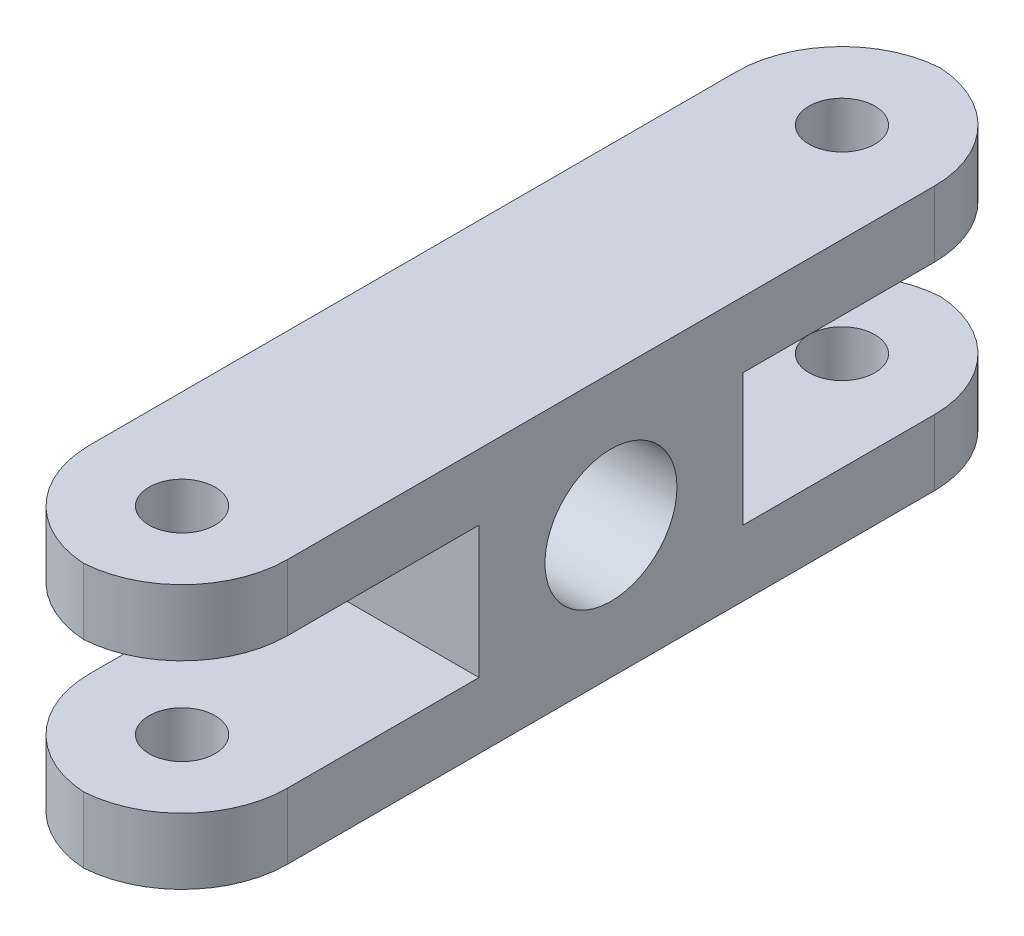
SolidWorks part; units mm, degrees
ref_plane "Front Plane" through (0, 0, 0) normal (0, 0, 1) x (1, 0, 0)
ref_plane "Top Plane" through (0, 0, 0) normal (0, 1, 0) x (1, 0, 0)
ref_plane "Right Plane" through (0, 0, 0) normal (1, 0, 0) x (0, 0, -1)
sketch "Sketch1" plane through (0, 0, 0) normal (0, 1, 0) x (1, 0, 0)
  line L1 (-7.5, -32.5) -> (7.5, -32.5)
  line L2 (-7.5, -32.5) -> (-7.5, 32.5)
  line L3 (-7.5, 32.5) -> (7.5, 32.5)
  line L4 (7.5, -32.5) -> (7.5, 32.5)
  line L5 (-7.5, -32.5) -> (7.5, 32.5) construction
  line L6 (-7.5, 32.5) -> (7.5, -32.5) construction
  point P0 (0, 0)
  dimension "D1" = 15
  dimension "D2" = 65
extrude "Boss-Extrude1" add sketch "Sketch1" along normal blind 20
sketch "Sketch2" plane through (0, 20, 0) normal (0, 1, 0) x (1, 0, 0)
  line L0 (-7.5, 0) -> (7.5, 0)
  line L1 (-7.5, 32.5) -> (-7.5, -32.5) construction
  line L2 (7.5, -32.5) -> (7.5, 32.5) construction
  line L3 (7.5, -32.5) -> (7.5, 32.5) construction
  circle A0 centre (0, 25) radius 2.5
  circle A1 centre (0, -25) radius 2.5
  dimension "D1" = 5
  dimension "D2" = 7.5
  dimension "D3" = 25
extrude "Cut-Extrude1" cut sketch "Sketch2" against normal blind 20 contours A0 | A1 region at (0, 20, -25)
sketch "Sketch6" plane through (7.5, 0, 0) normal (1, 0, 0) x (0, 0, -1)
  line L0 (-32.5, 20) -> (-32.5, 0) construction
  line L1 (-32.5, 0) -> (32.5, 0) construction
  circle A0 centre (0, 10) radius 5
  dimension "D1" = 10
  dimension "D2" = 32.5
  dimension "D3" = 10
extrude "Cut-Extrude3" cut sketch "Sketch6" against normal blind 15 contours A0
sketch "Sketch7" plane through (7.5, 0, 0) normal (1, 0, 0) x (0, 0, -1)
  line L0 (0, 20) -> (0, 0)
  line L1 (-32.5, 20) -> (32.5, 20) construction
  line L2 (-32.5, 0) -> (32.5, 0) construction
  line L3 (-10, 20) -> (-10, 0)
  line L4 (10, 20) -> (10, 0)
  line L5 (-10, 15) -> (-32.5, 15)
  line L6 (-32.5, 20) -> (-32.5, 0) construction
  line L7 (-32.5, 10) -> (-10, 10)
  line L8 (-10, 5) -> (-32.5, 5)
  line L9 (-32.5, 15) -> (-32.5, 20)
  line L10 (-32.5, 20) -> (-10, 20)
  line L11 (-10, 5) -> (-32.5, 5)
  line L12 (-32.5, 0) -> (-10, 0)
  line L13 (-32.5, 5) -> (-32.5, 0)
  line L14 (32.5, 5) -> (32.5, 0)
  line L15 (32.5, 0) -> (10, 0)
  line L16 (10, 5) -> (32.5, 5)
  line L17 (10, 15) -> (32.5, 15)
  line L18 (32.5, 15) -> (32.5, 20)
  line L19 (32.5, 20) -> (10, 20)
  line L20 (10, 20) -> (10, 0)
  point P8 (0, 10)
  point P15 (-32.5, 10)
  line M12 (32.5, 0) -> (32.5, 20)
  line M14 (-32.5, 20) -> (-32.5, 0)
  dimension "D1" = 10
  dimension "D2" = 5
extrude "Cut-Extrude4" cut sketch "Sketch7" against normal blind 15 contours L7 L3 L5 M14 | L8 L3 L7 M14 | L17 L4 L16 M12 region at (7.5, 12.5, 21.25) region at (7.5, 7.5, 21.25) region at (7.5, 10, -21.25)
fillet "Fillet3" radius 8 8 edges at (-7.5, 2.5, 32.5) (7.5, 2.5, 32.5) (7.5, 2.5, -32.5) (-7.5, 2.5, -32.5) (7.5, 17.5, -32.5) (-7.5, 17.5, -32.5) (-7.5, 17.5, 32.5) (7.5, 17.5, 32.5)
